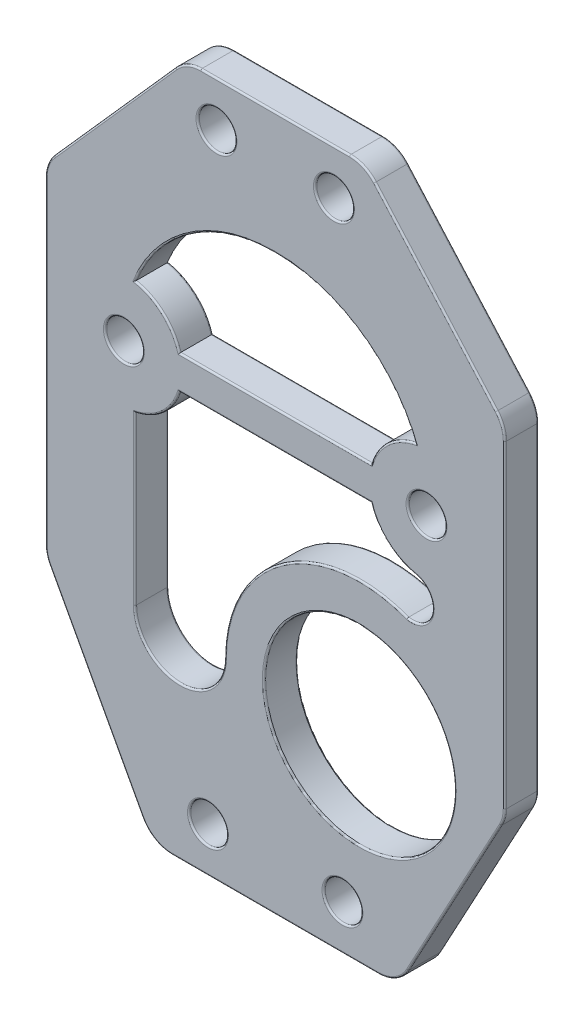
SolidWorks part; units mm, degrees
ref_plane "Front Plane" through (0, 0, 0) normal (0, 0, 1) x (1, 0, 0)
ref_plane "Top Plane" through (0, 0, 0) normal (0, 1, 0) x (1, 0, 0)
ref_plane "Right Plane" through (0, 0, 0) normal (1, 0, 0) x (0, 0, -1)
sketch "Sketch1" plane through (0, 0, 0) normal (0, 0, 1) x (1, 0, 0)
  line L0 (0, 0) -> (0, 62) construction
  line L1 (11, 0) -> (-11, 0)
  line L2 (-11, 0) -> (-20.5, 17.5997)
  line L3 (-20.5, 17.5997) -> (-20.5, 47.8997)
  line L4 (-20.5, 47.8997) -> (-7.9898, 62)
  line L5 (-7.9898, 62) -> (7.9898, 62)
  line L6 (20.5, 47.8997) -> (7.9898, 62)
  line L7 (11, 0) -> (20.5, 17.5997)
  line L8 (20.5, 17.5997) -> (20.5, 47.8997)
  line L9 (7.5, 17.5997) -> (20.5, 17.5997) construction
  line L10 (13.5, 37.5997) -> (-13.5, 37.5997) construction
  line L11 (-8.5472, 39.0997) -> (8.5472, 39.0997)
  line L12 (8.5472, 36.0997) -> (-8.5472, 36.0997) construction
  line L13 (8.5472, 36.0997) -> (8.5472, 39.0997) construction
  line L14 (8.5472, 39.0997) -> (-8.5472, 39.0997) construction
  line L15 (-8.5472, 36.0997) -> (-8.5472, 39.0997) construction
  line L16 (8.5472, 36.0997) -> (-8.5472, 39.0997) construction
  line L17 (8.5472, 39.0997) -> (-8.5472, 36.0997) construction
  line L18 (8.5472, 36.0997) -> (-8.5472, 36.0997)
  line L19 (13.5, 37.5997) -> (11.7833, 28.8092) construction
  line L20 (-12.5081, 32.5207) -> (-12.5081, 17.5997)
  circle A0 centre (-13.5, 37.5997) radius 1.675
  circle A1 centre (-5.2398, 58) radius 1.675
  circle A2 centre (-6, 4) radius 1.675
  circle A3 centre (6, 4) radius 1.675
  circle A4 centre (13.5, 37.5997) radius 1.675
  circle A5 centre (5.2398, 58) radius 1.675
  circle A6 centre (7.5, 17.5997) radius 8.5
  circle A7 centre (13.5, 37.5997) radius 5.175 construction
  circle A8 centre (-13.5, 37.5997) radius 5.175 construction
  circle A9 centre (7.5, 17.5997) radius 12 construction
  arc A10 (-12.5081, 42.6788) -> (12.5081, 42.6788) centre (0, 37.5997) cw
  arc A11 (12.5081, 42.6788) -> (8.5472, 39.0997) centre (13.5, 37.5997) ccw
  arc A12 (-12.5081, 42.6788) -> (-8.5472, 39.0997) centre (-13.5, 37.5997) cw
  arc A13 (-8.5472, 36.0997) -> (-12.5081, 32.5207) centre (-13.5, 37.5997) cw
  arc A14 (8.5472, 36.0997) -> (12.5081, 32.5207) centre (13.5, 37.5997) ccw
  arc A15 (11.7833, 28.8092) -> (12.5081, 32.5207) centre (12.1457, 30.6649) ccw
  arc A16 (11.7833, 28.8092) -> (-4.5, 17.5997) centre (7.5, 17.5997) ccw
  arc A17 (-12.5081, 17.5997) -> (-4.5, 17.5997) centre (-8.5041, 17.5997) ccw
  dimension "D2" = 3.35
  dimension "D10" = 17
  dimension "D19" = 13.5
  dimension "D1" = 62
  dimension "D3" = 6
  dimension "D4" = 4
  dimension "D5" = 20
  dimension "D6" = 30.3
  dimension "D7" = 7
  dimension "D8" = 10.3
  dimension "D9" = 11
  dimension "D11" = 2.75
  dimension "D12" = 4
  dimension "D13" = 18.85
  dimension "D14" = 20.5
  dimension "D15" = 13
  dimension "D20" = 3
  dimension "D16" = 3.5
  dimension "D17" = 3.5
  dimension "D18" = 3.5
extrude "Boss-Extrude1" add sketch "Sketch1" along normal blind 3
fillet "Fillet1" radius 3 8 edges at (-20.5, 47.8997, 1.5) (-7.9898, 62, 1.5) (7.9898, 62, 1.5) (20.5, 47.8997, 1.5) (-20.5, 17.5997, 1.5) (-11, 0, 1.5) (20.5, 17.5997, 1.5) (11, 0, 1.5)
fillet "Fillet2" radius 0.15 68 edges at (0.6956, 27.484, 0) (-8.5041, 13.5957, 0) (-12.5081, 25.0602, 0) (-10.0305, 33.76, 0) (0, 36.0997, 0) (10.0305, 33.76, 0) (14.0014, 30.3025, 0) (3.5648, 58, 0) (4.325, 4, 0) (-4.325, 4, 0) (-11.825, 37.5997, 0) (-20.4086, 17.6228, 0) (-15.9951, 9.2539, 0) (-10.7472, 0.4237, 0) (0, 0, 0) (10.7472, 0.4237, 0) (15.9951, 9.2539, 0) (20.4086, 17.6228, 0) (20.5, 32.5592, 0) (20.3047, 47.8256, 0) (14.3146, 54.8714, 0) (7.8712, 61.7361, 0) (0, 62, 0) (-7.8712, 61.7361, 0) (-14.3146, 54.8714, 0) (-20.3047, 47.8256, 0) (-20.5, 32.5592, 0) (-3.5648, 58, 0) (16, 17.5997, 0) (10.0305, 41.4394, 0) (0, 39.0997, 0) (-10.0305, 41.4394, 0) (0, 51.0997, 0) (11.825, 37.5997, 0) (0, 36.0997, 3) (-10.0305, 33.76, 3) (-12.5081, 25.0602, 3) (-8.5041, 13.5957, 3) (0.6956, 27.484, 3) (14.0014, 30.3025, 3) (10.0305, 33.76, 3) (16, 17.5997, 3) (-4.325, 4, 3) (-3.5648, 58, 3) (-11.825, 37.5997, 3) (-7.8712, 61.7361, 3) (0, 62, 3) (7.8712, 61.7361, 3) (14.3146, 54.8714, 3) (20.3047, 47.8256, 3) (20.5, 32.5592, 3) (20.4086, 17.6228, 3) (15.9951, 9.2539, 3) (10.7472, 0.4237, 3) (0, 0, 3) (-10.7472, 0.4237, 3) (-15.9951, 9.2539, 3) (-20.4086, 17.6228, 3) (-20.5, 32.5592, 3) (-20.3047, 47.8256, 3) (-14.3146, 54.8714, 3) (0, 39.0997, 3) (10.0305, 41.4394, 3) (0, 51.0997, 3) (-10.0305, 41.4394, 3) (4.325, 4, 3) (11.825, 37.5997, 3) (3.5648, 58, 3)
